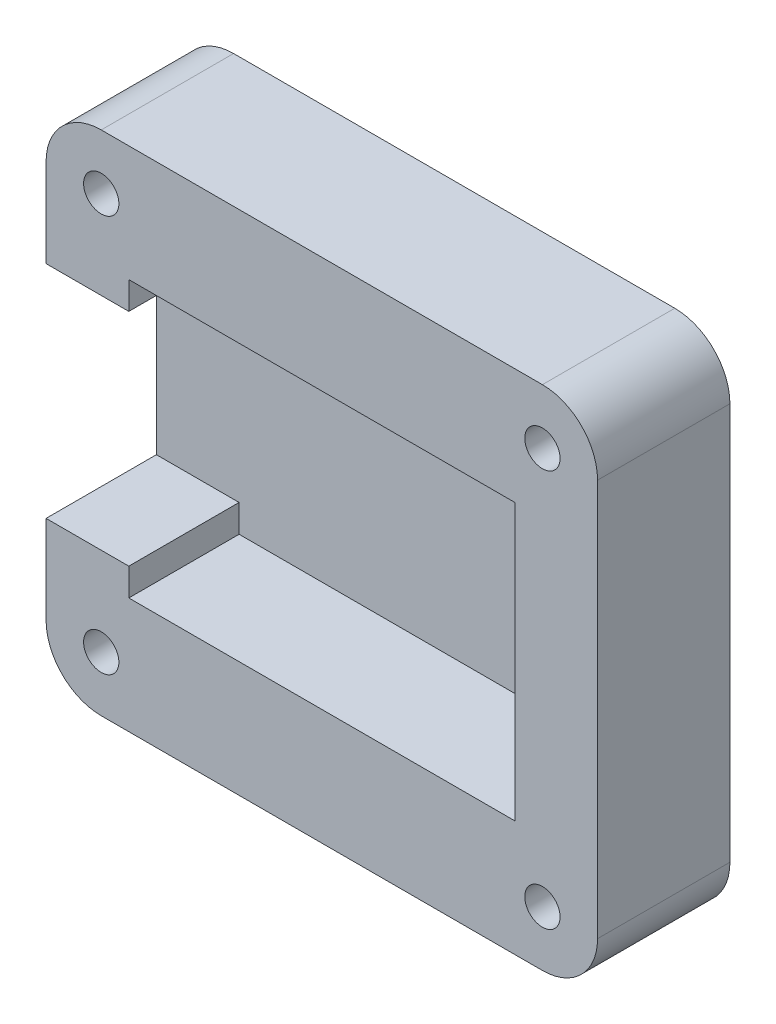
SolidWorks part; units mm, degrees
material "PVC hart"
ref_plane "Ebene vorne" through (0, 0, 0) normal (0, 0, 1) x (1, 0, 0)
ref_plane "Ebene oben" through (0, 0, 0) normal (0, 1, 0) x (1, 0, 0)
ref_plane "Ebene rechts" through (0, 0, 0) normal (1, 0, 0) x (0, 0, -1)
sketch "Skizze1" plane through (0, 0, 0) normal (0, 0, 1) x (1, 0, 0)
  line L0 (-12.5, 0) -> (12.5, 0) construction
  line L1 (-12.5, 11.5) -> (12.5, 11.5)
  line L2 (-12.5, 11.5) -> (-12.5, -11.5)
  line L3 (-12.5, -11.5) -> (12.5, -11.5)
  line L4 (12.5, 11.5) -> (12.5, -11.5)
  line L5 (0, 6.25) -> (0, -6.25) construction
  line L6 (-8.75, 6.25) -> (8.75, 6.25)
  line L7 (-8.75, 6.25) -> (-8.75, -6.25)
  line L8 (-8.75, -6.25) -> (8.75, -6.25)
  line L9 (8.75, 6.25) -> (8.75, -6.25)
  line L10 (-10, 9) -> (10, -9) construction
  line L11 (-10, 9) -> (10, 9) construction
  line L12 (-10, 9) -> (-10, -9) construction
  line L13 (-10, -9) -> (10, -9) construction
  line L14 (10, 9) -> (10, -9) construction
  dimension "D5" = 2.5
  dimension "D1" = 12.5
  dimension "D2" = 17.5
  dimension "D3" = 20
  dimension "D4" = 2.5
  dimension "D6" = 18
extrude "Aufsatz-Linear austragen1" add sketch "Skizze1" against normal blind 6 contours L1 L4 L3 L2
extrude "Schnitt-Linear austragen1" cut sketch "Skizze1<3>" against normal blind 5 contours L7 L8 L9 L6
sketch "Skizze1<3>" plane through (0, 0, 0) normal (0, 0, 1) x (1, 0, 0) same geometry as "Skizze1"
sketch "Skizze2" plane through (0, 0, 0) normal (0, 0, 1) x (1, 0, 0)
  line L0 (-12.5, 11.5) -> (-12.5, -11.5) construction
  line L1 (-12.5, 5) -> (-8.75, 5)
  line L2 (-12.5, 5) -> (-12.5, -5)
  line L3 (-12.5, -5) -> (-8.75, -5)
  line L4 (-8.75, 5) -> (-8.75, -5)
  line L5 (-8.75, 6.25) -> (-8.75, -6.25) construction
  line L6 (-8.75, 0) -> (0, 0) construction
  dimension "D1" = 10
extrude "Schnitt-Linear austragen2" cut sketch "Skizze2" against normal up to surface (5 mm away) up to face at (0, 0, -5)
hole_wizard "Formsenkung für M3 Senkschraube mit Innensechskant1" positions "Skizze4" profile "Skizze3" countersink size "M3" standard "DIN" end condition through all
sketch "Skizze4" plane through (0, 0, -6) normal (0, 0, -1) x (-1, 0, 0)
  point P0 (-10, 9)
  point P3 (10, 9)
  point P6 (10, -9)
  point P9 (-10, -9)
sketch "Skizze3" plane through (10, 9, -6) normal (1, 0, 0) x (0, 1, 0)
  line L0 (0, 0) -> (0, 6)
  line L1 (0, 6) -> (0.8, 6)
  line L2 (0.8, 6) -> (0.8, 0.95)
  line L3 (0.8, 0.95) -> (1.75, 0)
  line L5 (1.75, 0) -> (0, 0)
  line L6 (-0.8, 0.95) -> (-1.75, 0) construction
  line L11 (0, -6.35) -> (0, 107.95) construction
  dimension "Bohrerdurchmesser" = 1.6
  dimension "Bohrungstiefe" = 6
  dimension "Senkdurchmesser (Oben)" = 3.5
  dimension "Senkwinkel (Oben)" = 90
fillet "Verrundung1" radius 2.5 4 edges at (-12.5, 11.5, -3) (-12.5, -11.5, -3) (12.5, -11.5, -3) (12.5, 11.5, -3)
